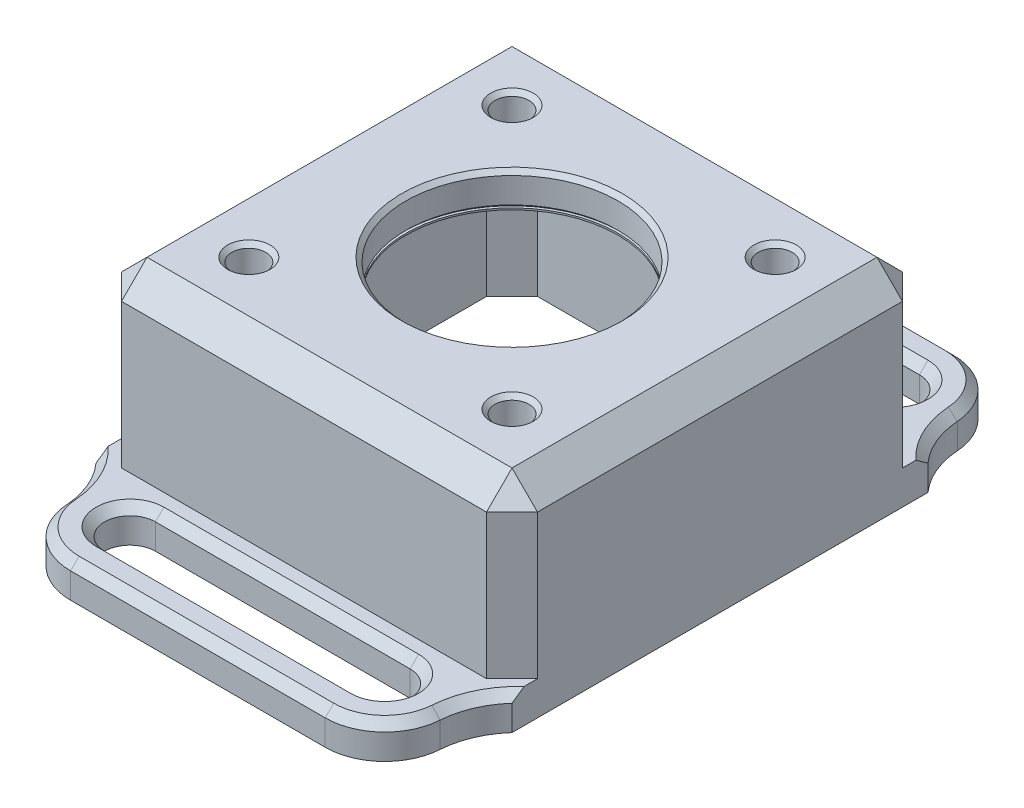
SolidWorks part; units mm, degrees
ref_plane "Front Plane" through (0, 0, 0) normal (0, 0, 1) x (1, 0, 0)
ref_plane "Top Plane" through (0, 0, 0) normal (0, 1, 0) x (1, 0, 0)
ref_plane "Right Plane" through (0, 0, 0) normal (1, 0, 0) x (0, 0, -1)
sketch "Sketch1" plane through (0, 0, 0) normal (0, 1, 0) x (1, 0, 0)
  line L0 (-24.5, 24.5) -> (-19.3301, 24.5)
  line L1 (-21.5, -21.5) -> (21.5, -21.5)
  line L2 (-21.5, -21.5) -> (-21.5, 21.5)
  line L3 (-21.5, 21.5) -> (21.5, 21.5)
  line L4 (21.5, -21.5) -> (21.5, 21.5)
  line L5 (-21.5, -21.5) -> (21.5, 21.5) construction
  line L6 (-21.5, 21.5) -> (21.5, -21.5) construction
  line L7 (-15.5, -15.5) -> (15.5, -15.5) construction
  line L8 (-15.5, -15.5) -> (-15.5, 15.5) construction
  line L9 (-15.5, 15.5) -> (15.5, 15.5) construction
  line L10 (15.5, -15.5) -> (15.5, 15.5) construction
  line L11 (-15.5, -15.5) -> (15.5, 15.5) construction
  line L12 (-15.5, 15.5) -> (15.5, -15.5) construction
  line L13 (24.5, -24.5) -> (24.5, 6.4372)
  line L14 (-24.5, -24.5) -> (-19.3301, -24.5)
  line L15 (-24.5, -24.5) -> (-24.5, 6.4372)
  line L19 (15, 30) -> (-15, 30) construction
  line L20 (15, 27) -> (-15, 27)
  line L21 (15, 33) -> (-15, 33)
  line L25 (-15, -30) -> (15, -30) construction
  line L26 (-15, -27) -> (15, -27)
  line L27 (-15, -33) -> (15, -33)
  line L28 (0, 30) -> (0, -30)
  line L31 (15, 37) -> (-15, 37)
  line L37 (-15, -37) -> (15, -37)
  line L38 (19.3301, 24.5) -> (24.5, 24.5)
  line L39 (-24.5, 24.5) -> (24.5, 24.5) construction
  line L40 (15, 23) -> (-15, 23) construction
  line L41 (19.3301, -24.5) -> (24.5, -24.5)
  line L42 (-24.5, -24.5) -> (24.5, -24.5) construction
  line L43 (-15, -23) -> (15, -23) construction
  line L45 (-24.5, -24.5) -> (-24.5, 24.5) construction
  line L46 (-24.5, 6.4372) -> (-24.5, 24.5)
  line L47 (24.5, 6.4372) -> (24.5, 24.5)
  line L48 (24.5, -24.5) -> (24.5, 24.5) construction
  arc A2 (15, 27) -> (15, 33) centre (15, 30) ccw
  arc A3 (-15, 33) -> (-15, 27) centre (-15, 30) ccw
  arc A6 (-15, -27) -> (-15, -33) centre (-15, -30) ccw
  arc A7 (15, -33) -> (15, -27) centre (15, -30) ccw
  arc A8 (-15, 37) -> (-19.3301, 24.5) centre (-15, 30) ccw
  arc A9 (19.3301, 24.5) -> (15, 37) centre (15, 30) ccw
  arc A14 (15, -37) -> (19.3301, -24.5) centre (15, -30) ccw
  arc A15 (-19.3301, -24.5) -> (-15, -37) centre (-15, -30) ccw
  arc A20 (-15, 37) -> (-15, 23) centre (-15, 30) ccw construction
  arc A21 (15, 23) -> (15, 37) centre (15, 30) ccw construction
  arc A22 (-15, -23) -> (-15, -37) centre (-15, -30) ccw construction
  arc A23 (15, -37) -> (15, -23) centre (15, -30) ccw construction
  point P0 (0, 0)
  point P6 (0, 0)
  point P22 (0, 30)
  point P36 (0, -30)
  point P43 (0, 0)
  dimension "D4" = 3
  dimension "D1" = 43
  dimension "D2" = 31
  dimension "D5" = 30
  dimension "D7" = 60
  dimension "D3" = 3
  dimension "D6" = 4
extrude "Boss-Extrude1" add sketch "Sketch1" along normal blind 4 contours L13 L47 L38 A9 L31 A8 L0 L46 L15 L14 A15 L37 A14 L41 A7 L27 A6 L26 L1 L2 L3 L20 A3 L21 A2 region at (-21.9151, 0, -23.6125)
sketch "Sketch2" plane through (0, 4, 0) normal (0, 1, 0) x (1, 0, 0)
  line L1 (-24.5, -24.5) -> (24.5, -24.5)
  line L2 (-24.5, -24.5) -> (-24.5, 24.5)
  line L3 (-24.5, 24.5) -> (24.5, 24.5)
  line L4 (24.5, -24.5) -> (24.5, 24.5)
  line L5 (-24.5, -24.5) -> (24.5, 24.5) construction
  line L6 (-24.5, 24.5) -> (24.5, -24.5) construction
  line L7 (-21.5, -21.5) -> (21.5, -21.5)
  line L8 (-21.5, -21.5) -> (-21.5, 21.5)
  line L9 (-21.5, 21.5) -> (21.5, 21.5)
  line L10 (21.5, -21.5) -> (21.5, 21.5)
  line L11 (-21.5, -21.5) -> (21.5, 21.5) construction
  line L12 (-21.5, 21.5) -> (21.5, -21.5) construction
  point P0 (0, 0)
  point P7 (0, 0)
extrude "Boss-Extrude2" add sketch "Sketch2" along normal blind 16
fillet "Fillet1" radius 10 4 edges at (19.3301, 2, 24.5) (19.3301, 2, -24.5) (-19.3301, 2, -24.5) (-19.3301, 2, 24.5)
sketch "Sketch3" plane through (0, 20, 0) normal (0, 1, 0) x (1, 0, 0)
  line L1 (-24.5, -24.5) -> (24.5, -24.5)
  line L2 (-24.5, -24.5) -> (-24.5, 24.5)
  line L3 (-24.5, 24.5) -> (24.5, 24.5)
  line L4 (24.5, -24.5) -> (24.5, 24.5)
  line L5 (-24.5, -24.5) -> (24.5, 24.5) construction
  line L6 (-24.5, 24.5) -> (24.5, -24.5) construction
  circle A0 centre (0, 0) radius 12.5
  point P0 (0, 0)
  dimension "D1" = 25
extrude "Boss-Extrude3" add sketch "Sketch3" along normal blind 4
hole_wizard "Ø4.0mm Dowel Hole1" positions "Sketch4" profile "Sketch6" hole size "Ø4.0" standard "ANSI Metric" end condition through all
sketch "Sketch4" plane through (0, 24, 0) normal (0, 1, 0) x (1, 0, 0)
  point P0 (15.5, 15.5)
  point P3 (-15.5, 15.5)
  point P6 (-15.5, -15.5)
  point P9 (15.5, -15.5)
sketch "Sketch6" plane through (15.5, 24, -15.5) normal (1, 0, 0) x (0, 0, 1)
  line L0 (0, 0) -> (0, 24)
  line L1 (0, 24) -> (2, 24)
  line L2 (2, 24) -> (2, 0)
  line L5 (2, 0) -> (0, 0)
  line L11 (0, -6.35) -> (0, 107.95) construction
  dimension "Thru Hole Dia." = 4
  dimension "Thru Hole Depth" = 24
sketch "Sketch7" plane through (0, 4, 0) normal (0, 1, 0) x (1, 0, 0)
  line L1 (-44.6636, 24.5) -> (-24.5, 24.5)
  line L2 (-44.6636, 24.5) -> (-44.6636, -24.5)
  line L3 (-44.6636, -24.5) -> (-24.5, -24.5)
  line L4 (-24.5, 24.5) -> (-24.5, -24.5)
  line L5 (43.1912, -25.2276) -> (24.5, -25.2276)
  line L6 (43.1912, -25.2276) -> (43.1912, 24.5)
  line L7 (43.1912, 24.5) -> (24.5, 24.5)
  line L8 (24.5, -25.2276) -> (24.5, 24.5)
extrude "Cut-Extrude1" [suppressed] cut sketch "Sketch7" against normal blind 4
chamfer "Chamfer1" distance 3 angle 45 12 edges at (0, 24, 24.5) (24.5, 14, 24.5) (24.5, 24, 0) (24.5, 14, -24.5) (0, 24, -24.5) (-24.5, 14, -24.5) (-24.5, 24, 0) (-24.5, 14, 24.5) (-21.5, 10, -21.5) (21.5, 10, -21.5) (21.5, 10, 21.5) (-21.5, 10, 21.5)
chamfer "Chamfer2" [suppressed] distance 1 angle 45
chamfer "Chamfer3" distance 0.5 angle 45 6 edges at (-15.5, 24, -13.5) (-15.5, 24, 17.5) (15.5, 24, 17.5) (15.5, 24, -13.5) (0, 20, 12.5) (0, 24, 12.5)
chamfer "Chamfer4" distance 1 angle 45 18 edges at (22.7439, 4, -27.279) (-22.7439, 4, -27.279) (19.778, 4, -35.1157) (-19.778, 4, -35.1157) (0, 4, -37) (-22.7439, 4, 27.279) (22.7439, 4, 27.279) (-19.778, 4, 35.1157) (19.778, 4, 35.1157) (0, 4, 37) (0, 4, 27) (-18, 4, 30) (18, 4, 30) (0, 4, 33) (0, 4, -33) (18, 4, -30) (-18, 4, -30) (0, 4, -27)
sketch "Sketch8" plane through (0, 20, 0) normal (0, -1, 0) x (1, 0, 0)
  line L1 (19.3579, 18.5284) -> (-19.3579, 18.5284)
  line L2 (19.3579, 18.5284) -> (19.3579, -18.5284)
  line L3 (19.3579, -18.5284) -> (-19.3579, -18.5284)
  line L4 (-19.3579, 18.5284) -> (-19.3579, -18.5284)
  line L5 (19.3579, 18.5284) -> (-19.3579, -18.5284) construction
  line L6 (19.3579, -18.5284) -> (-19.3579, 18.5284) construction
  point P0 (0, 0)
extrude "Boss-Extrude4" add sketch "Sketch8" against normal blind 0.2
sketch "Sketch9" plane through (0, 20.2, 0) normal (0, 1, 0) x (1, 0, 0)
  circle A0 centre (0, 0) radius 12.5
extrude "Cut-Extrude2" cut sketch "Sketch9" against normal through all
sketch "Sketch10" plane through (0, 20.2, 0) normal (0, 1, 0) x (1, 0, 0)
  circle A0 centre (-15.5, 15.5) radius 2
  circle A1 centre (-15.5, -15.5) radius 2
  circle A2 centre (15.5, -15.5) radius 2
  circle A3 centre (15.5, 15.5) radius 2
extrude "Cut-Extrude3" cut sketch "Sketch10" against normal through all
